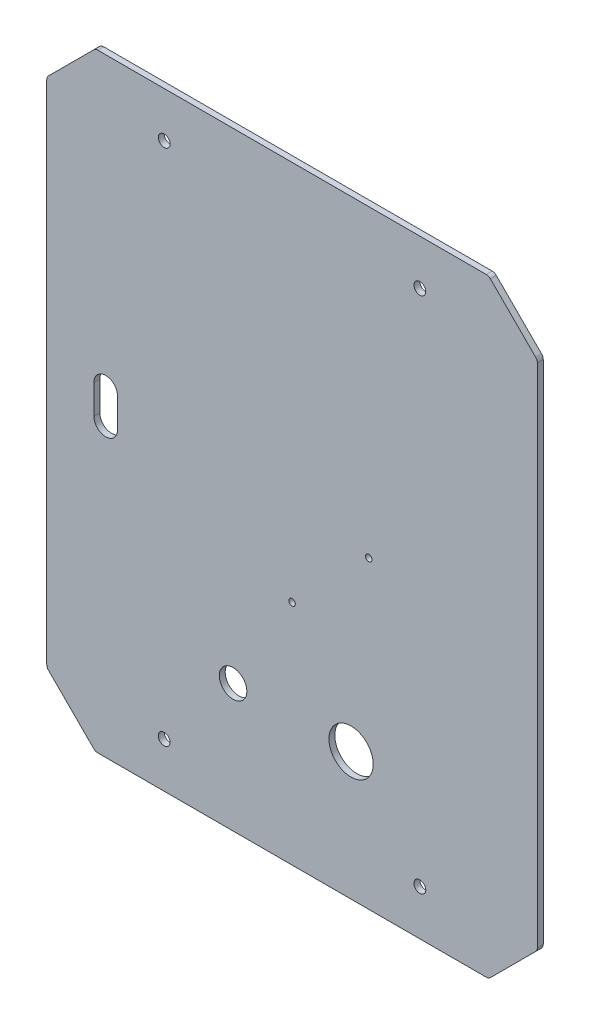
SolidWorks part; units mm, degrees
material "Alliage 1060"
ref_plane "Plan de dessus" through (0, 0, 0) normal (0, 0, 1) x (1, 0, 0)
ref_plane "Plan de droite" through (0, 0, 0) normal (0, 1, 0) x (1, 0, 0)
ref_plane "Plan de face" through (0, 0, 0) normal (1, 0, 0) x (0, 0, -1)
sketch "Esquisse1" plane through (0, 0, 0) normal (0, 0, 1) x (1, 0, 0)
  line L0 (0, 0) -> (-200, 0)
  line L1 (-200, 0) -> (-224.7487, 24.7487)
  line L2 (-224.7487, 24.7487) -> (-224.7487, 284.7487)
  line L3 (-224.7487, 284.7487) -> (-200, 309.4975)
  line L4 (-200, 309.4975) -> (0, 309.4975)
  line L5 (0, 309.4975) -> (24.7487, 284.7487)
  line L6 (24.7487, 284.7487) -> (24.7487, 24.7487)
  line L7 (24.7487, 24.7487) -> (0, 0)
  dimension "D1" = 260
  dimension "D2" = 35
  dimension "D3" = 135
  dimension "D4" = 200
extrude "Base" add sketch "Esquisse1" along normal blind 3
fillet "Congé1" radius 3 8 edges at (-200, 0, 1.5) (-224.7487, 24.7487, 1.5) (-224.7487, 284.7487, 1.5) (-200, 309.4975, 1.5) (0, 309.4975, 1.5) (24.7487, 284.7487, 1.5) (24.7487, 24.7487, 1.5) (0, 0, 1.5)
sketch "Esquisse19" plane through (0, 0, 0) normal (0, 0, -1) x (-1, 0, 0)
  line L0 (100, 309.4975) -> (100, 0) construction
  line L1 (1.2426, 309.4975) -> (198.7574, 309.4975) construction
  line L2 (198.7574, 0) -> (1.2426, 0) construction
  line L3 (-24.7487, 154.7487) -> (224.7487, 154.7487) construction
  line L4 (-24.7487, 25.9914) -> (-24.7487, 283.5061) construction
  line L5 (224.7487, 283.5061) -> (224.7487, 25.9914) construction
sketch "Esquisse20" plane through (0, 0, 0) normal (0, 0, -1) x (-1, 0, 0)
  line L0 (35, 286.4975) -> (35, 309.4975) construction
  line L1 (1.2426, 309.4975) -> (198.7574, 309.4975) construction
  line L2 (35, 286.4975) -> (100, 286.4975) construction
  line L3 (100, 309.4975) -> (100, 0) construction
  line L4 (100, 309.4975) -> (100, 0) construction
  line L5 (198.7574, 0) -> (1.2426, 0) construction
  line L6 (-24.7487, 154.7487) -> (224.7487, 154.7487) construction
  line L7 (-24.7487, 25.9914) -> (-24.7487, 283.5061) construction
  circle A0 centre (35, 286.4975) radius 3
  circle A1 centre (165, 286.4975) radius 3
  circle A2 centre (165, 23) radius 3
  circle A3 centre (35, 23) radius 3
  dimension "D3" = 6
  dimension "D1" = 65
  dimension "D2" = 23
extrude "Perçage Profilés" cut sketch "Esquisse20" against normal through all
sketch "Esquisse21" plane through (0, 0, 0) normal (0, 0, -1) x (-1, 0, 0)
  line L1 (100, 154.7487) -> (100, 115.7487) construction
  line L2 (100, 309.4975) -> (100, 0) construction
  line L3 (100, 154.7487) -> (61, 154.7487) construction
  line L4 (-24.7487, 154.7487) -> (224.7487, 154.7487) construction
  circle A1 centre (61, 154.7487) radius 1.65
  circle A2 centre (100, 115.7487) radius 1.65
  dimension "D2" = 3.3
  dimension "D1" = 39
extrude "Perçage Lidar" cut sketch "Esquisse21" against normal through all
sketch "Esquisse22" plane through (0, 0, 0) normal (0, 0, -1) x (-1, 0, 0)
  line L0 (100, 309.4975) -> (100, 0) construction
  line L1 (198.7574, 0) -> (1.2426, 0) construction
  circle A0 centre (70, 65) radius 11.25
  point P2 (33.9273, 57.4798)
  point P3 (50.9605, 57.9986)
  dimension "D1" = 22.5
  dimension "D2" = 30
  dimension "D3" = 65
extrude "Perçage Arret d'urgence" cut sketch "Esquisse22" against normal through all
sketch "Esquisse23" plane through (0, 0, 0) normal (0, 0, -1) x (-1, 0, 0)
  line L0 (198.7574, 0) -> (1.2426, 0) construction
  line L1 (100, 309.4975) -> (100, 0) construction
  circle A0 centre (130, 65) radius 7
  dimension "D1" = 14
  dimension "D2" = 65
  dimension "D3" = 30
extrude "Perçage Tirette" cut sketch "Esquisse23" against normal through all
sketch "Esquisse24" plane through (0, 0, 0) normal (0, 0, -1) x (-1, 0, 0)
  line L0 (194.7487, 147.2487) -> (194.7487, 162.2487) construction
  line L1 (188.7487, 147.2487) -> (188.7487, 162.2487)
  line L2 (200.7487, 147.2487) -> (200.7487, 162.2487)
  line L3 (-24.7487, 154.7487) -> (224.7487, 154.7487) construction
  line L4 (224.7487, 283.5061) -> (224.7487, 25.9914) construction
  arc A0 (188.7487, 147.2487) -> (200.7487, 147.2487) centre (194.7487, 147.2487) ccw
  arc A1 (200.7487, 162.2487) -> (188.7487, 162.2487) centre (194.7487, 162.2487) ccw
  point P2 (194.7487, 154.7487)
  point P7 (0, 0)
  dimension "D1" = 6
  dimension "D2" = 15
  dimension "D3" = 30
extrude "Perçage Cable management" cut sketch "Esquisse24" against normal through all
